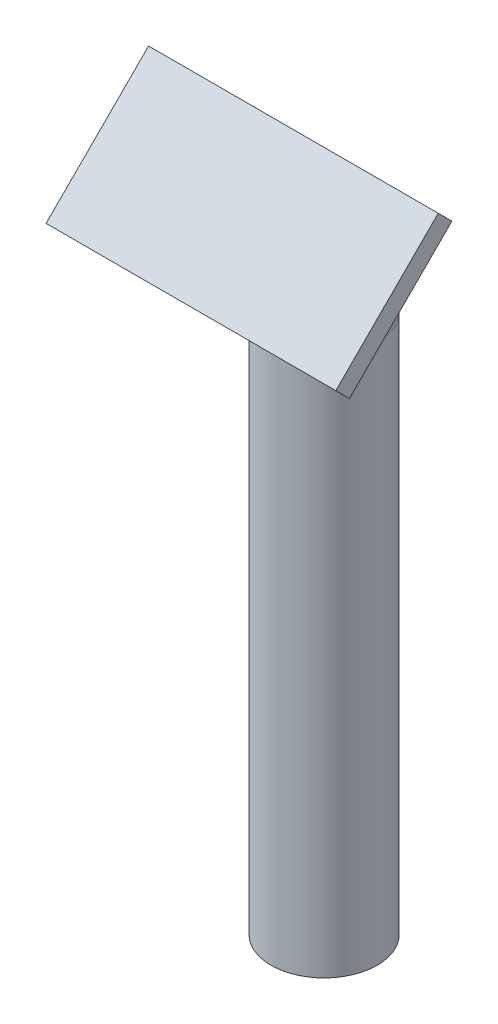
SolidWorks part; units mm, degrees
material "Ductile Iron"
ref_plane "Front Plane" through (0, 0, 0) normal (0, 0, 1) x (1, 0, 0)
ref_plane "Top Plane" through (0, 0, 0) normal (0, 1, 0) x (1, 0, 0)
ref_plane "Right Plane" through (0, 0, 0) normal (1, 0, 0) x (0, 0, -1)
sketch "Sketch1" [suppressed] plane through (0, 0, 0) normal (0, 1, 0) x (1, 0, 0)
  circle A0 centre (0, 0) radius 55
  dimension "D1" = 110
sketch "Sketch2" plane through (0, 0, 0) normal (1, 0, 0) x (0, 0, -1)
  line L0 (0, 0) -> (0, 558.5786)
  line L1 (-29.2893, 629.2893) -> (-70.7107, 670.7107)
  arc A0 (0, 558.5786) -> (-29.2893, 629.2893) centre (-100, 558.5786) ccw
  point P6 (0, 600)
  dimension "D4" = 100
  dimension "D1" = 600
  dimension "D2" = 135
  dimension "D3" = 100
sweep "Sweep-Thin1" add path "Sketch2" circular profile diameter 110 parameters "D1"=2, "D3"=110
sketch "Sketch69" plane through (0, 370.7107, 370.7107) normal (0, 0.7071, 0.7071) x (1, 0, 0)
  line L1 (-150, 349.2641) -> (150, 349.2641)
  line L2 (-150, 349.2641) -> (-150, 499.2641)
  line L3 (-150, 499.2641) -> (150, 499.2641)
  line L4 (150, 349.2641) -> (150, 499.2641)
  line L5 (-150, 349.2641) -> (150, 499.2641) construction
  line L6 (-150, 499.2641) -> (150, 349.2641) construction
  point P0 (0, 424.2641)
  dimension "D1" = 300
  dimension "D2" = 150
extrude "Boss-Extrude1" add sketch "Sketch69" along normal blind 20
